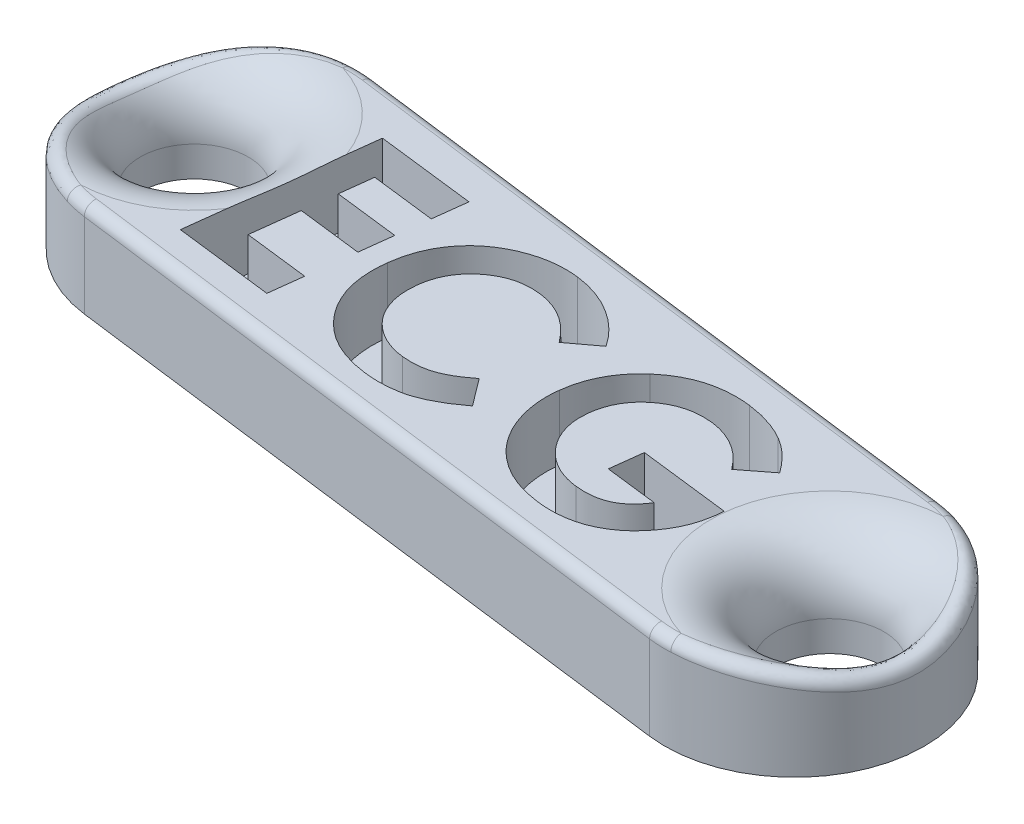
SolidWorks part; units mm, degrees
ref_plane "Front Plane" through (0, 0, 0) normal (0, 0, 1) x (1, 0, 0)
ref_plane "Top Plane" through (0, 0, 0) normal (0, 1, 0) x (1, 0, 0)
ref_plane "Right Plane" through (0, 0, 0) normal (1, 0, 0) x (0, 0, -1)
sketch "Sketch1" plane through (0, 0, 0) normal (0, 1, 0) x (1, 0, 0)
  line L0 (-7.5, 0.9601) -> (7.5, -0.9601) construction
  line L1 (-7.1191, 3.9359) -> (7.8809, 2.0156)
  line L2 (-7.8809, -2.0156) -> (7.1191, -3.9359)
  arc A0 (-7.1191, 3.9359) -> (-7.8809, -2.0156) centre (-7.5, 0.9601) ccw
  arc A1 (7.1191, -3.9359) -> (7.8809, 2.0156) centre (7.5, -0.9601) ccw
  point P2 (0, 0)
  dimension "D1" = 6
  dimension "D2" = 15
extrude "Boss-Extrude1" add sketch "Sketch1" along normal blind 2.2
sketch "Sketch2" plane through (0, 2.2, 0) normal (0, 1, 0) x (1, 0, 0)
  line L0 (-9.8025, -0.9631) -> (9.2437, -3.4013) construction
  line L1 (-7.8809, -2.0156) -> (7.1191, -3.9359) construction
  arc A0 (-7.1191, 3.9359) -> (-7.8809, -2.0156) centre (-7.5, 0.9601) ccw construction
  arc A1 (7.1191, -3.9359) -> (7.8809, 2.0156) centre (7.5, -0.9601) ccw construction
  text T0 "<b>ECG</b>" font "Century Gothic" height in points 16
  dimension "D1" = 0
  dimension "D2" = 0.8
sketch "Sketch3" plane through (0, 2.2, 0) normal (0, 1, 0) x (1, 0, 0)
  line L0 (-7.8809, -2.0156) -> (7.1191, -3.9359) construction
  circle A0 centre (-8.4312, 1.0794) radius 1.25
  circle A1 centre (8.4312, -1.0794) radius 1.25
  dimension "D1" = 2.5
  dimension "D2" = 2.5
  dimension "D3" = 3
  dimension "D4" = 3
  dimension "D5" = 8.5
  dimension "D6" = 8.5
extrude "Cut-Extrude1" cut sketch "Sketch3" against normal blind 3
extrude "Cut-Extrude2" cut sketch "Sketch2" against normal blind 1.5
fillet "Fillet1" radius 1.5 2 edges at (8.4312, 2.2, 2.3294) (-8.4312, 2.2, 0.1706)
fillet "Fillet7" radius 0.25 8 edges at (8.499, 2.2, -1.8687) (10.4995, 2.0398, 0.9076) (7.7541, 2.2, 3.9494) (-8.499, 2.2, 1.8687) (-10.4995, 2.0398, -0.9076) (-7.7541, 2.2, -3.9494) (-0.3809, 2.2, 2.9757) (0.3809, 2.2, -2.9757)
